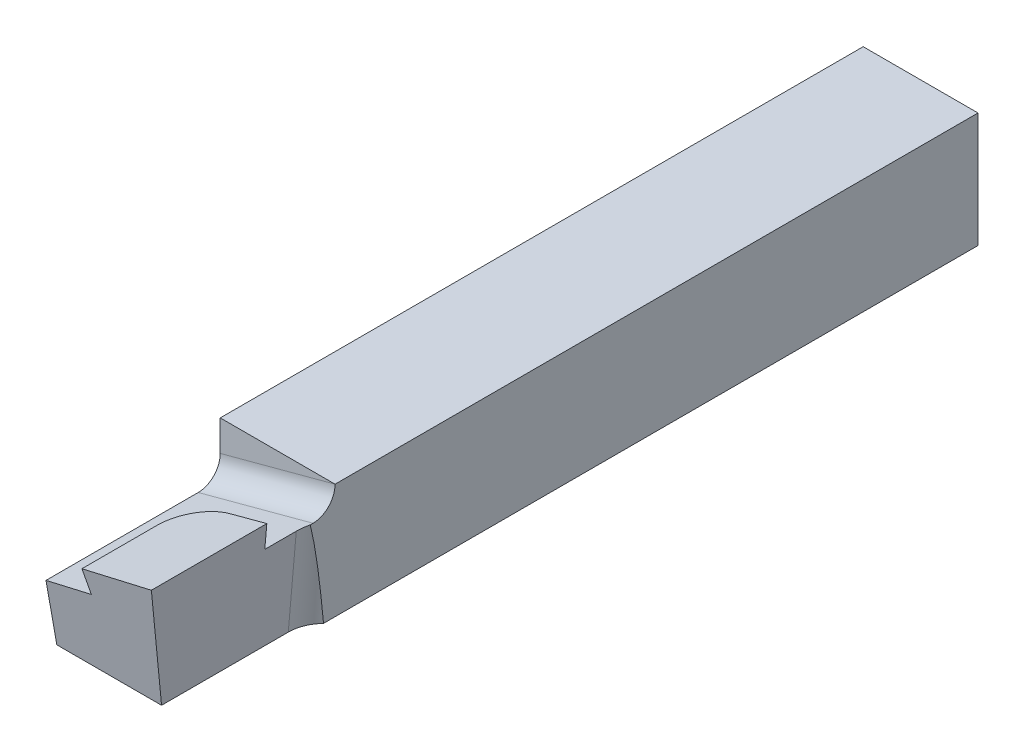
SolidWorks part; units mm, degrees
ref_plane "Front Plane" through (0, 0, 0) normal (0, 0, 1) x (1, 0, 0)
ref_plane "Top Plane" through (0, 0, 0) normal (0, 1, 0) x (1, 0, 0)
ref_plane "Right Plane" through (0, 0, 0) normal (1, 0, 0) x (0, 0, -1)
sketch "Sketch1" plane through (0, 0, 0) normal (0, 0, 1) x (1, 0, 0)
  line L1 (-3.9688, -3.9688) -> (3.9688, -3.9688)
  line L2 (-3.9688, -3.9688) -> (-3.9688, 3.9688)
  line L3 (-3.9688, 3.9688) -> (3.9688, 3.9688)
  line L4 (3.9688, -3.9688) -> (3.9688, 3.9688)
  line L5 (-3.9688, -3.9688) -> (3.9688, 3.9688) construction
  line L6 (-3.9688, 3.9688) -> (3.9688, -3.9688) construction
  point P0 (0, 0)
  dimension "D1" = 7.9375
extrude "Boss-Extrude1" add sketch "Sketch1" along normal blind 57.15
sketch "Sketch2" plane through (0, 0, 57.15) normal (0, 0, 1) x (1, 0, 0)
  line L0 (-3.9688, 1.8419) -> (3.9688, 3.9688)
  line L1 (-3.9688, 3.9688) -> (-3.9688, -3.9688) construction
  line L2 (3.9688, 3.9688) -> (3.2743, -3.9688)
  line L3 (-3.9688, -3.9688) -> (3.9688, -3.9688) construction
  line L4 (3.2743, -3.9688) -> (-3.9688, -3.9688)
  line L5 (-3.9688, -3.9688) -> (-3.9688, 1.8419)
  line L6 (3.9688, 3.9688) -> (-3.9688, 3.9688) construction
  line L7 (3.9688, -3.9688) -> (3.9688, 3.9688) construction
  dimension "D1" = 15
  dimension "D2" = 5
extrude "Cut-Extrude1" cut sketch "Sketch2" against normal blind 12.7 flip side to cut
fillet "Fillet1" [suppressed] radius 2.54
fillet "Fillet2" radius 2.54 1 edges at (3.6215, 0, 44.45)
sketch "Sketch3" plane through (3.9688, 0, 0) normal (1, 0, 0) x (0, 0, -1)
  line L0 (-57.15, 3.9688) -> (-55.7504, -3.9688)
  line L1 (-46.99, -3.9688) -> (-57.15, -3.9688) construction
  line L2 (-55.7504, -3.9688) -> (-57.15, -3.9688)
  line L3 (-57.15, -3.9688) -> (-57.15, 3.9688)
  dimension "D1" = 10
extrude "Cut-Extrude2" cut sketch "Sketch3" against normal through all
sketch "Sketch4" plane through (-0.7263, 2.7107, 0) normal (-0.2588, 0.9659, 0) x (0.9659, 0.2588, 0)
  line L0 (4.8607, -57.15) -> (-3.3568, -56.775) construction
  line L1 (4.8607, -46.99) -> (4.8607, -57.15) construction
  line L2 (-5.9766, -44.45) -> (8.8954, -44.45)
  line L3 (4.8607, -57.15) -> (-0.3572, -56.9119)
  line L4 (4.8607, -57.15) -> (4.8607, -49.1667)
  line L5 (4.8607, -49.1667) -> (2.1828, -49.1667)
  line L6 (-0.3572, -56.9119) -> (-0.3572, -51.7067)
  line L7 (-5.9766, -44.45) -> (-5.9766, -56.9119)
  line L8 (-5.9766, -56.9119) -> (-0.3572, -56.9119)
  line L9 (4.8607, -57.15) -> (8.8954, -57.15)
  line L10 (8.8954, -57.15) -> (8.8954, -44.45)
  arc A0 (2.1828, -49.1667) -> (-0.3572, -51.7067) centre (2.1828, -51.7067) ccw
  line M1 (-3.3568, -56.775) -> (4.8607, -57.15)
  line M2 (4.8607, -57.15) -> (4.8607, -46.99)
  line M4 (-3.3568, -44.45) -> (-3.3568, -56.775)
  line M12 (4.8607, -46.99) -> (4.8607, -44.45)
  line M13 (4.8607, -44.45) -> (-3.3568, -44.45)
  dimension "D1" = 2.54
extrude "Cut-Extrude3" cut sketch "Sketch4" against normal blind 1.524 contours L7 L8 L2 M1 M4 | A0 L5 L6 M2 M12 M13 M4 M1 | L9 L10 L2 M12 M2 region at (-5.2201, 1.5066, 50.7196) region at (-0.9285, 2.6565, 49.1313) region at (5.9173, 4.4909, 50.8)
fillet "Fillet3" radius 1.524 1 edges at (0, 1.3276, 44.45)
